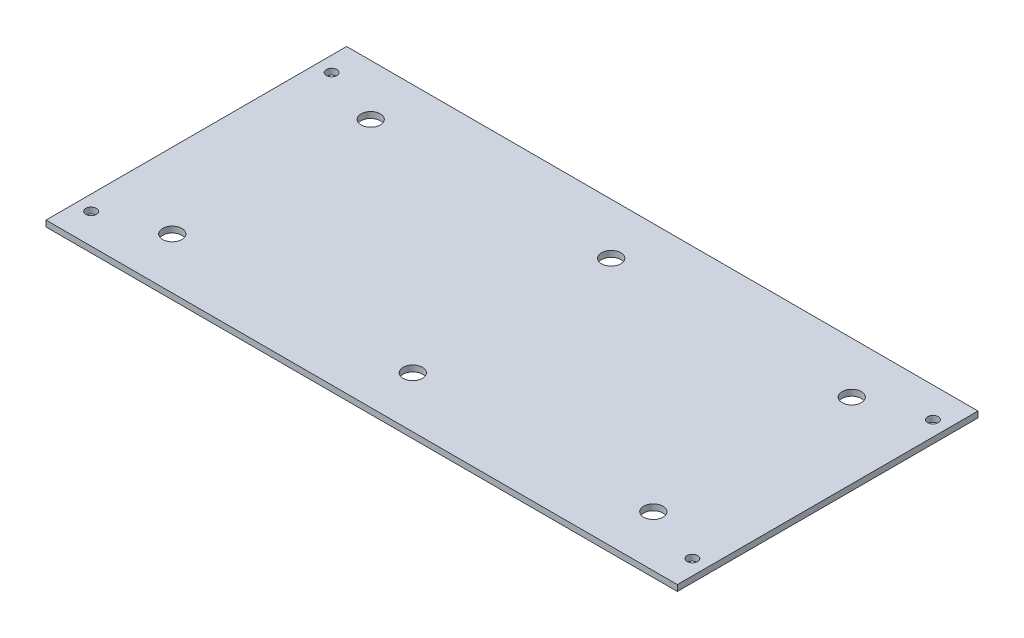
SolidWorks part; units mm, degrees
ref_plane "Спереди" through (0, 0, 0) normal (0, 0, 1) x (1, 0, 0)
ref_plane "Сверху" through (0, 0, 0) normal (0, 1, 0) x (1, 0, 0)
ref_plane "Справа" through (0, 0, 0) normal (1, 0, 0) x (0, 0, -1)
sketch "Эскиз1" plane through (0, 0, 0) normal (0, 1, 0) x (1, 0, 0)
  line L5 (0, 0) -> (210, 0)
  line L6 (0, 0) -> (0, 100)
  line L7 (0, 100) -> (210, 100)
  line L8 (210, 0) -> (210, 100)
  line L9 (0, 50) -> (210, 50) construction
  line L10 (105, 100) -> (105, 0) construction
  circle A0 centre (105, 17) radius 3.2
  circle A1 centre (185, 17) radius 3.2
  circle A2 centre (25, 17) radius 3.2
  circle A3 centre (25, 83) radius 3.2
  circle A4 centre (105, 83) radius 3.2
  circle A5 centre (185, 83) radius 3.2
  circle A6 centre (5, 10) radius 1.75
  circle A7 centre (5, 90) radius 1.75
  circle A8 centre (205, 10) radius 1.75
  circle A9 centre (205, 90) radius 1.75
  point P16 (0, 0)
  dimension "D3" = 17
  dimension "D5" = 6.4
  dimension "D6" = 6.4
  dimension "D7" = 3.5
  dimension "D1" = 210
  dimension "D2" = 100
  dimension "D4" = 80
  dimension "D8" = 10
  dimension "D9" = 5
extrude "Бобышка-Вытянуть1" add sketch "Эскиз1" along normal blind 2
